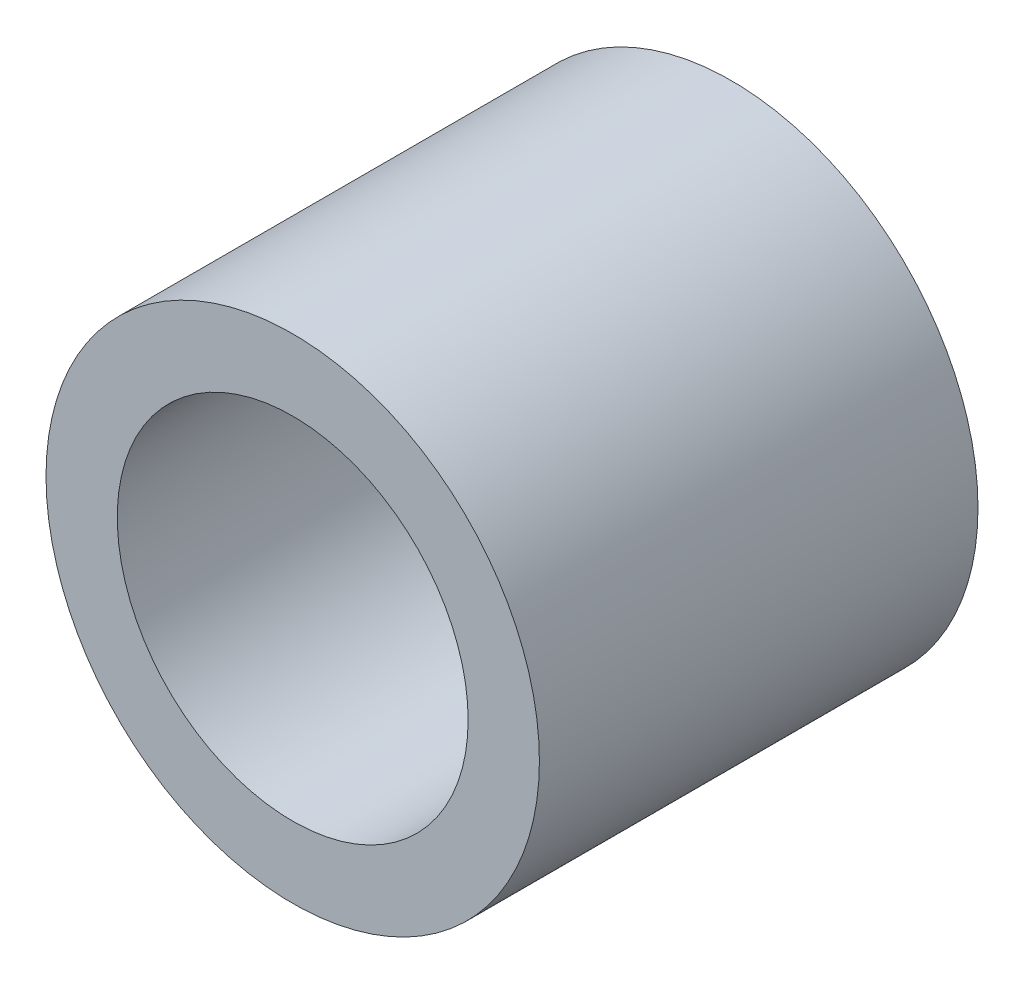
SolidWorks part; units mm, degrees
ref_plane "Front Plane" through (0, 0, 0) normal (0, 0, 1) x (1, 0, 0)
ref_plane "Top Plane" through (0, 0, 0) normal (0, 1, 0) x (1, 0, 0)
ref_plane "Right Plane" through (0, 0, 0) normal (1, 0, 0) x (0, 0, -1)
sketch "Sketch1" plane through (0, 0, 0) normal (0, 0, 1) x (1, 0, 0)
  line L0 (0, 1.6) -> (0, 2.25) construction
  line L1 (0, -1.6) -> (0, -2.25) construction
  circle A0 centre (0, 0) radius 2.25
  circle A1 centre (0, 0) radius 1.6
  dimension "OD" = 4.5
  dimension "ID" = 3.2
sketch "Sketch2" plane through (0, 0, 0) normal (1, 0, 0) x (0, 0, -1)
  line L0 (-2, 1.6) -> (2, 1.6) construction
  line L1 (-2, -1.6) -> (2, -1.6) construction
  line L2 (-2, -2.25) -> (2, -2.25) construction
  line L3 (-2, 2.25) -> (2, 2.25) construction
  dimension "Length" = 4
extrude "Extrude1" add sketch "Sketch1" along normal up to vertex (2 mm away) and the other way up to vertex (2 mm away) up to point (0, 1.6, 2) other way up to point (0, 1.6, -2)
sketch "Sketch3" plane through (0, 0, 2) normal (0, 0, 1) x (1, 0, 0)
  circle A0 centre (0, 0) radius 1.6 construction
  circle A3 centre (0, 0) radius 1.6
  point P3 (-1.6, 0)
